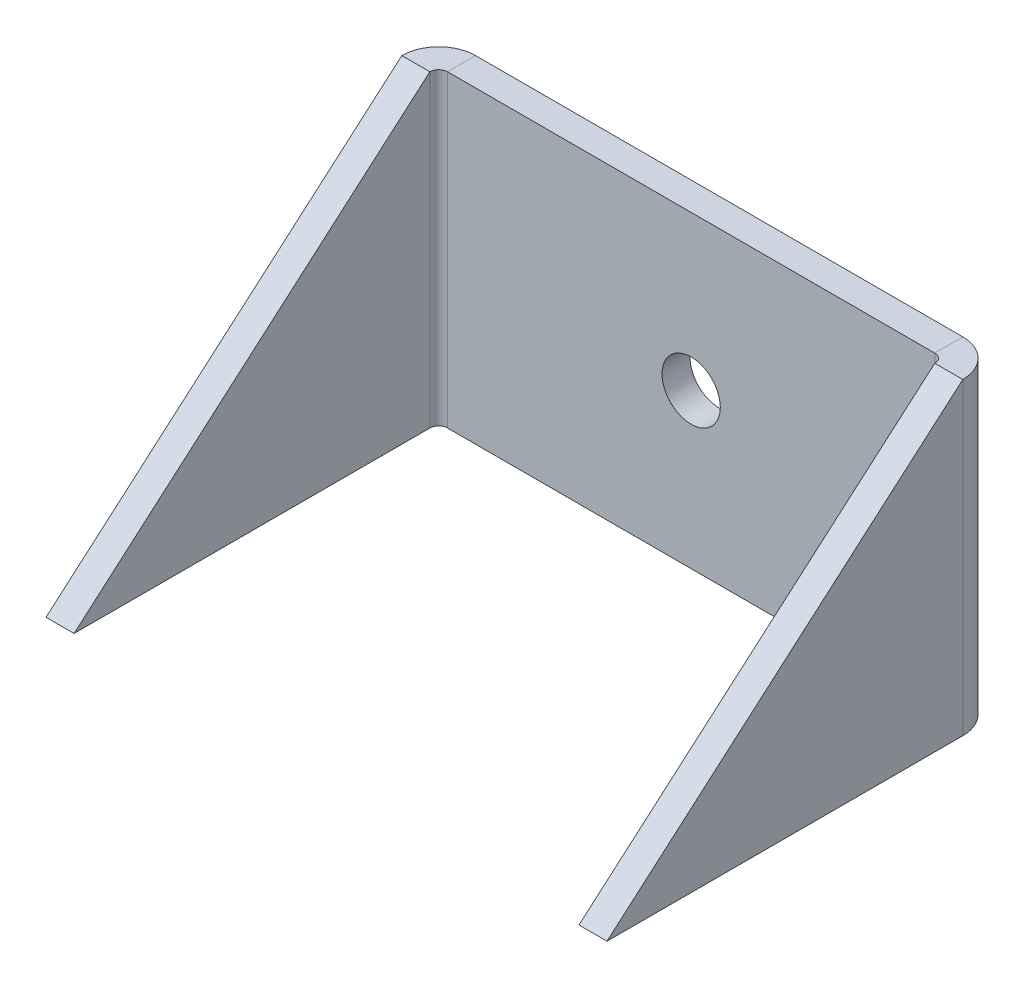
SolidWorks part; units mm, degrees
note: The reader was unsure of these and kept them because the rebuilt part matched: flange length of "Edge-Flange1".
material "6061-T6 (SS)"
ref_plane "X-Y Datum" through (0, 0, 0) normal (0, 0, 1) x (1, 0, 0)
ref_plane "X-Z Datum" through (0, 0, 0) normal (0, 1, 0) x (1, 0, 0)
ref_plane "Y-Z Datum" through (0, 0, 0) normal (1, 0, 0) x (0, 0, -1)
sketch "Sketch2" plane through (0, 0, 0) normal (0, 0, 1) x (1, 0, 0)
  line L1 (-28.575, 17.4625) -> (28.575, 17.4625)
  line L2 (-28.575, 17.4625) -> (-28.575, -17.4625)
  line L3 (-28.575, -17.4625) -> (28.575, -17.4625)
  line L4 (28.575, 17.4625) -> (28.575, -17.4625)
  line L5 (-28.575, 17.4625) -> (28.575, -17.4625) construction
  line L6 (-28.575, -17.4625) -> (28.575, 17.4625) construction
  circle A0 centre (0, 0) radius 3 construction
  point P0 (0, 0)
  dimension "D3" = 6
  dimension "D1" = 34.925
  dimension "D2" = 57.15
base flange "Base-Flange1" sketch "Sketch2" thickness 3.175 reverse thickness direction yes parameters "D1"=1
edge flange "Edge-Flange1" sketch "Sketch9" flange angle 90 flange length 44.45 flange position material outside bend radius 1 thickness 3.175 relief rectangular parameters "D6"=10
sketch "Sketch9" plane through (28.575, 0, 3.175) normal (1, 0, 0) x (0, 1, 0)
  line L2 (-17.4625, 0) -> (-17.4625, 41.275)
  line L3 (-17.4625, 41.275) -> (17.4625, 41.275)
  line L4 (17.4625, 41.275) -> (17.4625, 0)
  line L7 (-17.4625, 0) -> (17.4625, 0) construction
  line L8 (-17.4625, 0) -> (17.4625, 0)
bend "EdgeBend1" bend radius 1 bend angle 90 parameters "D5"=1
sketch "Sketch10" plane through (31.75, 0, 0) normal (1, 0, 0) x (0, 0, -1)
  line L0 (-4.175, 17.4625) -> (-44.45, -17.4625)
  line L1 (-44.45, 17.4625) -> (-44.45, -17.4625) construction
  line L3 (-44.45, -17.4625) -> (-4.175, -17.4625) construction
  line L7 (-4.175, -17.4625) -> (-4.175, 17.4625)
  line L8 (-4.175, 17.4625) -> (-44.45, 17.4625)
  line L9 (-44.45, 17.4625) -> (-44.45, -17.4625)
  line L10 (-44.45, -17.4625) -> (-4.175, -17.4625)
  line L12 (-4.175, 17.4625) -> (-44.45, 17.4625)
  line L13 (-44.45, 17.4625) -> (-44.45, -17.4625)
  dimension "D1" = 0
extrude "Cut-Extrude1" cut sketch "Sketch10" against normal blind 3.175 normal cut yes
mirror "Mirror1" about plane through (0, 0, 0) normal (1, 0, 0) of "Cut-Extrude1", "Edge-Flange1"
bend "MirrorBend1" bend radius 1 bend angle 90 parameters "D5"=2
sketch "Sketch11" [suppressed] plane through (32.75, 0, 0) normal (1, 0, 0) x (0, 0, -1)
  line L0 (-4.175, -15.875) -> (-44.45, 15.875)
extrude "Cut-Extrude2" [suppressed] cut sketch "Sketch11" against normal blind 3.175 and the other way through all
hole_wizard "M6 Clearance Hole1" positions "Sketch13" profile "Sketch14" hole size "M6" standard "ANSI Metric" end condition through all
sketch "Sketch13" plane through (0, 0, 3.175) normal (0, 0, 1) x (1, 0, 0)
  point P0 (0, 0)
sketch "Sketch14" plane through (0, 0, 3.175) normal (1, 0, 0) x (0, -1, 0)
  line L0 (0, 0) -> (0, 3.175)
  line L1 (0, 3.175) -> (3.3, 3.175)
  line L2 (3.3, 3.175) -> (3.3, 0)
  line L5 (3.3, 0) -> (0, 0)
  line L11 (0, -6.35) -> (0, 107.95) construction
  dimension "Thru Hole Dia." = 6.6
  dimension "Thru Hole Depth" = 3.175
sketch "Bend-Lines1" [suppressed] plane through (0, 0, 0) normal (0, 1, 0) x (1, 0, 0)
sketch "Bounding-Box1" [suppressed] plane through (0, 0, 0) normal (0, 1, 0) x (1, 0, 0)
sheet metal parameters "Sheet-Metal1" thickness 3.175 parameters "D1"=1
flat pattern "Flat-Pattern1" [suppressed]
sketch "Bend-Lines2" plane through (0, 0, 0) normal (0, 1, 0) x (1, 0, 0)
sketch3d "Bounding-Box2" [suppressed]
  line L0 (-63.5, -15.875, 0) -> (63.5, -15.875, 0) construction
  line L1 (-63.5, 15.875, 0) -> (63.5, 15.875, 0) construction
  line L2 (-63.5, -15.875, 0) -> (-63.5, 15.875, 0) construction
  line L3 (63.5, -15.875, 0) -> (63.5, 15.875, 0) construction
sheet metal parameters "Sheet-Metal2" thickness 3.175 parameters "D1"=1
flat pattern "Flat-Pattern1"
sketch "Bend-Lines2" plane through (0, 0, 0) normal (0, 0, -1) x (-1, 0, 0)
  line L0 (-30.6072, 15.875) -> (-30.6072, -15.875) construction
  line L1 (-30.6072, 15.875) -> (-30.6072, -15.875) construction
sketch3d "Bounding-Box2" [suppressed]
  line L0 (28.575, -15.875, 0) -> (-72.9144, -15.875, 0) construction
  line L1 (28.575, 15.875, 0) -> (-72.9144, 15.875, 0) construction
  line L2 (28.575, -15.875, 0) -> (28.575, 15.875, 0) construction
  line L3 (-72.9144, -15.875, 0) -> (-72.9144, 15.875, 0) construction
bend of the flat pattern "Flatten-<EdgeBend1>1"
sheet metal parameters "Sheet-Metal5" thickness 3.175 parameters "D1"=1
flat pattern "Flat-Pattern1"
sketch "Bend-Lines2" plane through (0, 0, 0) normal (0, 0, -1) x (-1, 0, 0)
  line L0 (-29.6072, 15.875) -> (-29.6072, -15.875) construction
  line L1 (-29.6072, 15.875) -> (-29.6072, -15.875) construction
  line L2 (29.6072, -15.875) -> (29.6072, 15.875) construction
  line L3 (29.6072, -15.875) -> (29.6072, 15.875) construction
sketch3d "Bounding-Box2" [suppressed]
  line L0 (71.9144, -15.875, 0) -> (-71.9144, -15.875, 0) construction
  line L1 (71.9144, 15.875, 0) -> (-71.9144, 15.875, 0) construction
  line L2 (71.9144, -15.875, 0) -> (71.9144, 15.875, 0) construction
  line L3 (-71.9144, -15.875, 0) -> (-71.9144, 15.875, 0) construction
bend of the flat pattern "Flatten-<EdgeBend1>1"
bend of the flat pattern "Flatten-<MirrorBend1>1"
sheet metal parameters "Sheet-Metal7" thickness 3.175 parameters "D1"=1
flat pattern "Flat-Pattern1"
sketch "Bend-Lines2" plane through (0, 0, 0) normal (0, 0, -1) x (-1, 0, 0)
  line L0 (-30.6072, 15.875) -> (-30.6072, -15.875) construction
  line L1 (-30.6072, 15.875) -> (-30.6072, -15.875) construction
sketch3d "Bounding-Box2" [suppressed]
  line L0 (28.575, -15.875, 0) -> (-72.9144, -15.875, 0) construction
  line L1 (28.575, 15.875, 0) -> (-72.9144, 15.875, 0) construction
  line L2 (28.575, -15.875, 0) -> (28.575, 15.875, 0) construction
  line L3 (-72.9144, -15.875, 0) -> (-72.9144, 15.875, 0) construction
bend of the flat pattern "Flatten-<EdgeBend1>1"
sheet metal parameters "Sheet-Metal8" thickness 3.175 parameters "D1"=1
flat pattern "Flat-Pattern1"
sketch "Bend-Lines2" plane through (0, 0, 0) normal (0, 0, -1) x (-1, 0, 0)
  line L0 (-30.6072, 15.875) -> (-30.6072, -15.875) construction
  line L1 (-30.6072, 15.875) -> (-30.6072, -15.875) construction
sketch3d "Bounding-Box2" [suppressed]
  line L0 (28.575, -15.875, 0) -> (-72.9144, -15.875, 0) construction
  line L1 (28.575, 15.875, 0) -> (-72.9144, 15.875, 0) construction
  line L2 (28.575, -15.875, 0) -> (28.575, 15.875, 0) construction
  line L3 (-72.9144, -15.875, 0) -> (-72.9144, 15.875, 0) construction
bend of the flat pattern "Flatten-<EdgeBend1>1"
sheet metal parameters "Sheet-Metal9" thickness 3.175 parameters "D1"=1
flat pattern "Flat-Pattern1"
sketch "Bend-Lines2" plane through (0, 0, 0) normal (0, 0, -1) x (-1, 0, 0)
  line L0 (-29.6072, 15.875) -> (-29.6072, -15.875) construction
  line L1 (-29.6072, 15.875) -> (-29.6072, -15.875) construction
  line L2 (29.6072, -15.875) -> (29.6072, 15.875) construction
  line L3 (29.6072, -15.875) -> (29.6072, 15.875) construction
sketch3d "Bounding-Box2" [suppressed]
  line L0 (71.9144, -15.875, 0) -> (-71.9144, -15.875, 0) construction
  line L1 (71.9144, 15.875, 0) -> (-71.9144, 15.875, 0) construction
  line L2 (71.9144, -15.875, 0) -> (71.9144, 15.875, 0) construction
  line L3 (-71.9144, -15.875, 0) -> (-71.9144, 15.875, 0) construction
bend of the flat pattern "Flatten-<EdgeBend1>1"
bend of the flat pattern "Flatten-<MirrorBend1>1"
